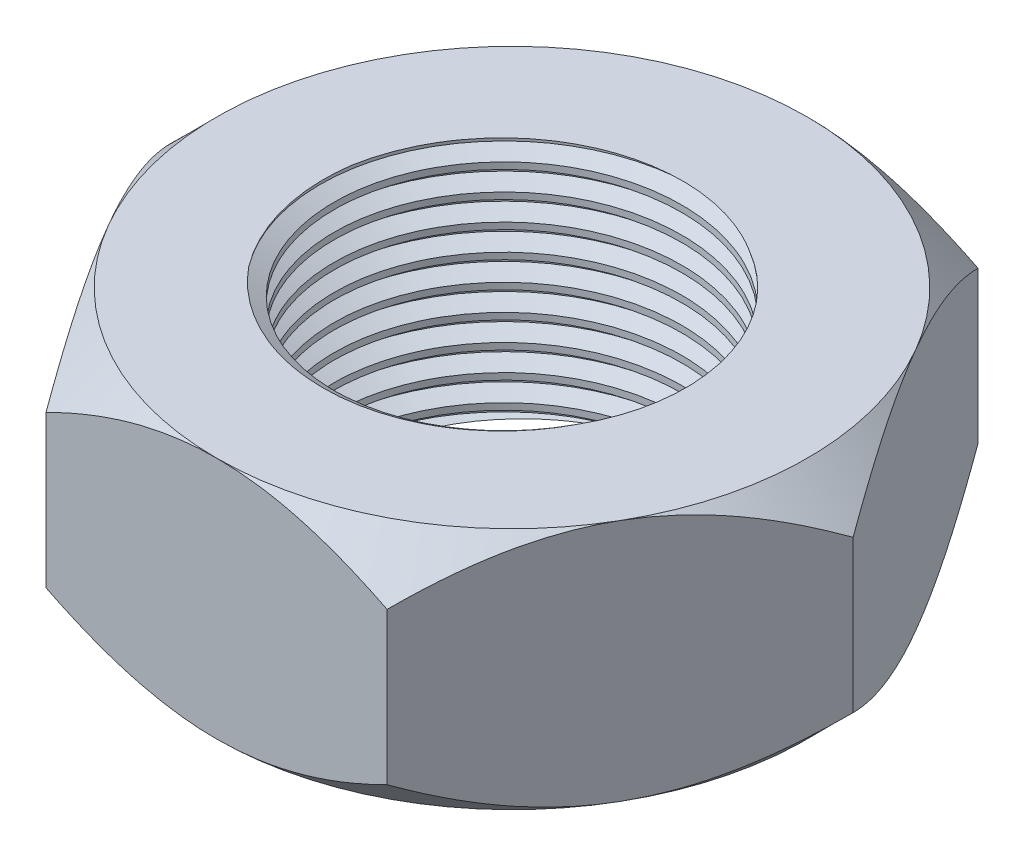
SolidWorks part; units mm, degrees
material "1023 Carbon Steel Sheet (SS)"
ref_plane "Front Plane" through (0, 0, 0) normal (0, 0, 1) x (1, 0, 0)
ref_plane "Top Plane" through (0, 0, 0) normal (0, 1, 0) x (1, 0, 0)
ref_plane "Right Plane" through (0, 0, 0) normal (1, 0, 0) x (0, 0, -1)
sketch "Sketch1" plane through (0, 0, 0) normal (0, 1, 0) x (1, 0, 0)
  line L1 (19.6299, 0) -> (9.815, 17)
  line L2 (9.815, 17) -> (-9.815, 17)
  line L3 (-9.815, 17) -> (-19.6299, 0)
  line L4 (-19.6299, 0) -> (-9.815, -17)
  line L5 (-9.815, -17) -> (9.815, -17)
  line L6 (9.815, -17) -> (19.6299, 0)
  circle A0 centre (0, 0) radius 17 construction
  dimension "D1" = 34
extrude "Boss-Extrude1" add sketch "Sketch1" along normal mid plane 14
sketch "Sketch2" plane through (0, 7, 0) normal (0, 1, 0) x (1, 0, 0)
  circle A0 centre (0, 0) radius 17
extrude "Cut-Extrude1" cut sketch "Sketch2" against normal mid plane 14 draft 45 flip side to cut
mirror "Mirror1" about plane through (0, 0, 0) normal (0, 1, 0) of "Cut-Extrude1"
sketch "Sketch3" plane through (0, 7, 0) normal (0, 1, 0) x (1, 0, 0)
  circle A0 centre (0, 0) radius 10
  dimension "D1" = 20
extrude "Cut-Extrude2" cut sketch "Sketch3" against normal up to next
thread "Thread1" pitch 1.5 method cut profile "Thread Profile1" start angle 0, offset 2, length 18, pitch 1.5, diameter 20
ref_plane "Plane1" through (-10, 9, 0) normal (0, 0, 1) x (-1, 0, 0)
sketch "Thread Profile1" plane through (-10, 9, 0) normal (0, 0, 1) x (-1, 0, 0)
  line L0 (0, 0) -> (0, 1.5) construction
  line L1 (0, 0) -> (0.8119, 0.4687)
  line L2 (0.8119, 0.4687) -> (0.8119, 0.6562)
  line L3 (0.8119, 0.6562) -> (0, 1.125)
  line L4 (0.8119, 0.5625) -> (0, 0.5625) construction
  line L11 (0, 0) -> (0, 1.125)
  point P2 (0, 0)
  dimension "Pitch" = 1.5
  dimension "Profile_Angle" = 60
  dimension "Profile_Land" = 0.1875
  dimension "Profile_Height" = 0.8119
